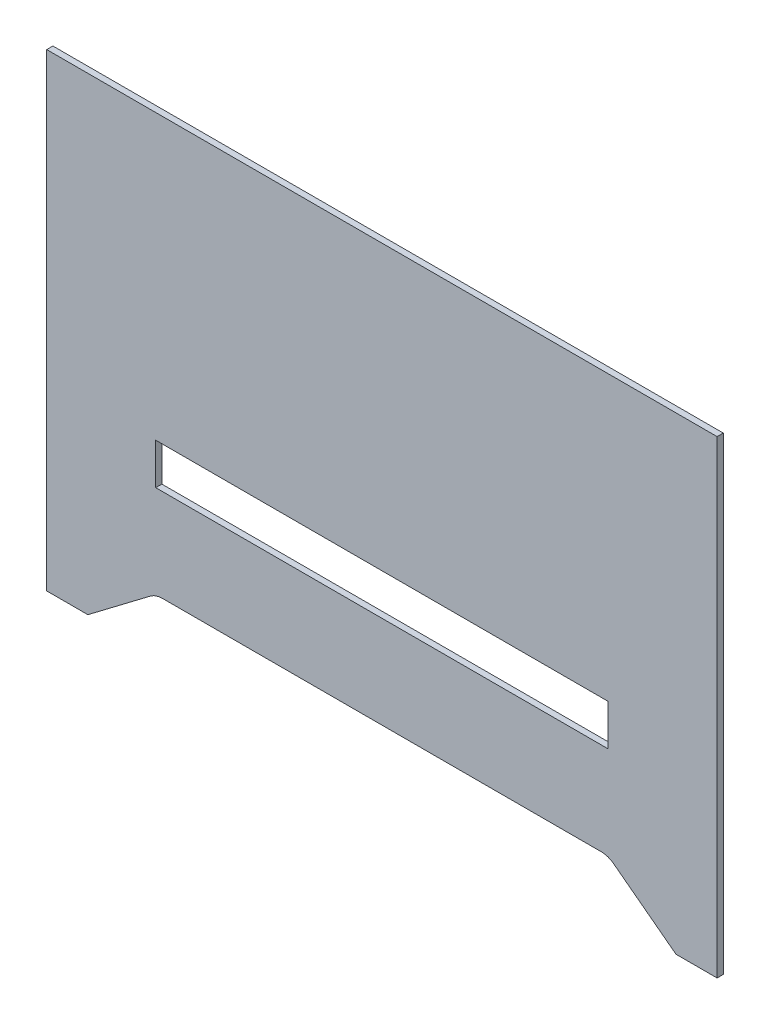
SolidWorks part; units mm, degrees
ref_plane "前视基准面" through (0, 0, 0) normal (0, 0, 1) x (1, 0, 0)
ref_plane "上视基准面" through (0, 0, 0) normal (0, 1, 0) x (1, 0, 0)
ref_plane "右视基准面" through (0, 0, 0) normal (1, 0, 0) x (0, 0, -1)
sketch "Sketch1" plane through (0, 0, 0) normal (0, 0, 1) x (1, 0, 0)
  line L0 (0, -114) -> (0, 0) construction
  line L1 (-163, -114) -> (163, -114) construction
  line L2 (-163, -114) -> (-163, 114)
  line L3 (-163, 114) -> (163, 114)
  line L4 (163, -114) -> (163, 114)
  line L5 (-163, -114) -> (163, 114) construction
  line L6 (-163, 114) -> (163, -114) construction
  line L7 (-106.6398, -89) -> (106.6398, -89)
  line L8 (112.6784, -91.0291) -> (143, -114)
  line L9 (143, -114) -> (163, -114)
  line L10 (-143, -114) -> (-163, -114)
  line L11 (-112.6784, -91.0291) -> (-143, -114)
  line L13 (-110, -44) -> (110, -44)
  line L14 (-110, -44) -> (-110, -24)
  line L15 (-110, -24) -> (110, -24)
  line L16 (110, -44) -> (110, -24)
  line L17 (-110, -44) -> (110, -24) construction
  line L18 (-110, -24) -> (110, -44) construction
  arc A0 (112.6784, -91.0291) -> (106.6398, -89) centre (106.6398, -99) ccw
  arc A1 (-112.6784, -91.0291) -> (-106.6398, -89) centre (-106.6398, -99) cw
  point P0 (0, 0)
  point P8 (0, -34)
  point P13 (110, -89)
  point P18 (0, -89)
  dimension "D6" = 10
  dimension "D1" = 326
  dimension "D2" = 228
  dimension "D3" = 25
  dimension "D4" = 20
  dimension "D5" = 110
  dimension "D7" = 220
  dimension "D8" = 20
  dimension "D9" = 138
extrude "Boss-Extrude1" add sketch "Sketch1" along normal blind 3
